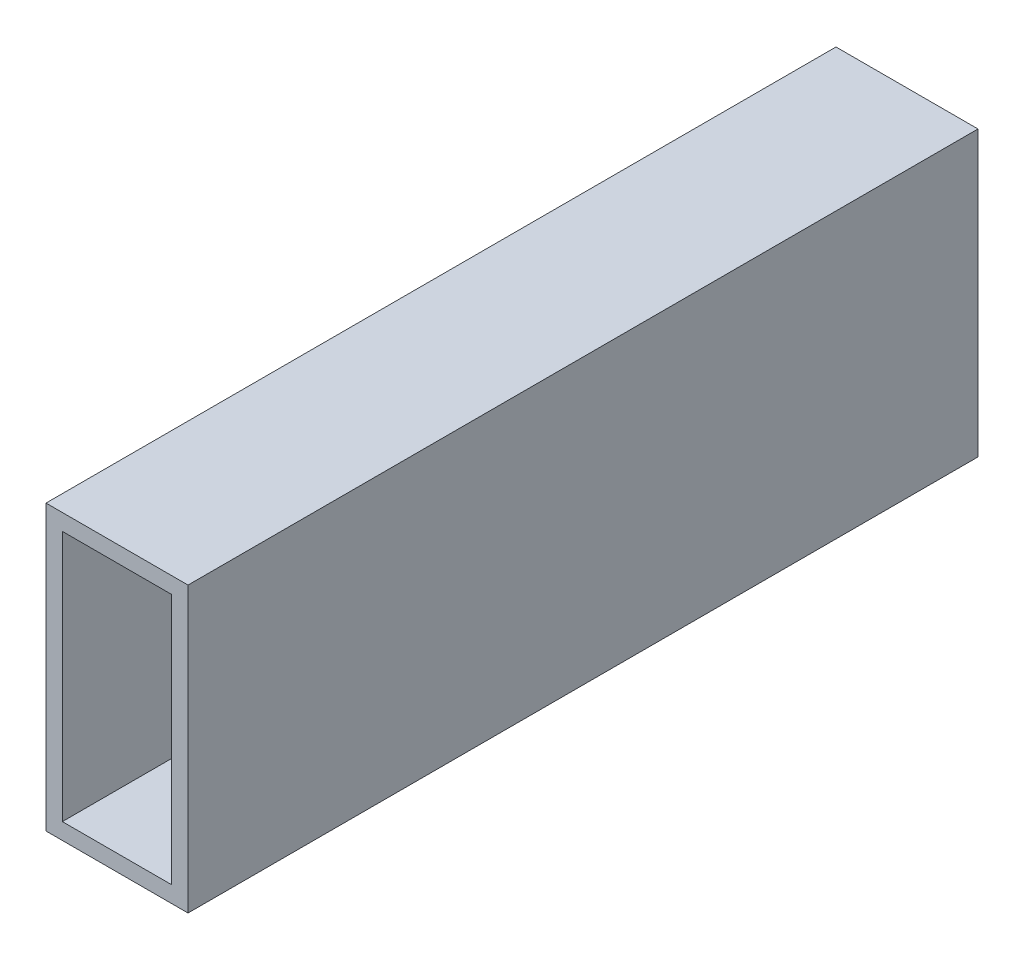
SolidWorks part; units mm, degrees
material "6061 Alloy"
ref_plane "Front Plane" through (0, 0, 0) normal (0, 0, 1) x (1, 0, 0)
ref_plane "Top Plane" through (0, 0, 0) normal (0, 1, 0) x (1, 0, 0)
ref_plane "Right Plane" through (0, 0, 0) normal (1, 0, 0) x (0, 0, -1)
sketch "Sketch1" plane through (0, 0, 0) normal (0, 0, 1) x (1, 0, 0)
  line L0 (-9.779, 22.479) -> (9.779, 22.479)
  line L1 (-12.7, -25.4) -> (12.7, -25.4)
  line L2 (-12.7, -25.4) -> (-12.7, 25.4)
  line L3 (-12.7, 25.4) -> (12.7, 25.4)
  line L4 (12.7, -25.4) -> (12.7, 25.4)
  line L5 (-12.7, -25.4) -> (12.7, 25.4) construction
  line L6 (-12.7, 25.4) -> (12.7, -25.4) construction
  line L7 (9.779, -22.479) -> (9.779, 22.479)
  line L8 (-9.779, -22.479) -> (9.779, -22.479)
  line L9 (-9.779, -22.479) -> (-9.779, 22.479)
  point P0 (0, 0)
  dimension "D1" = 25.4
  dimension "D2" = 50.8
  dimension "D3" = 2.921
extrude "Boss-Extrude1" add sketch "Sketch1" along normal blind 141.2875
equation "\"length\"= 5.5625"
equation "\"D1@Boss-Extrude1\"=\"length\""
